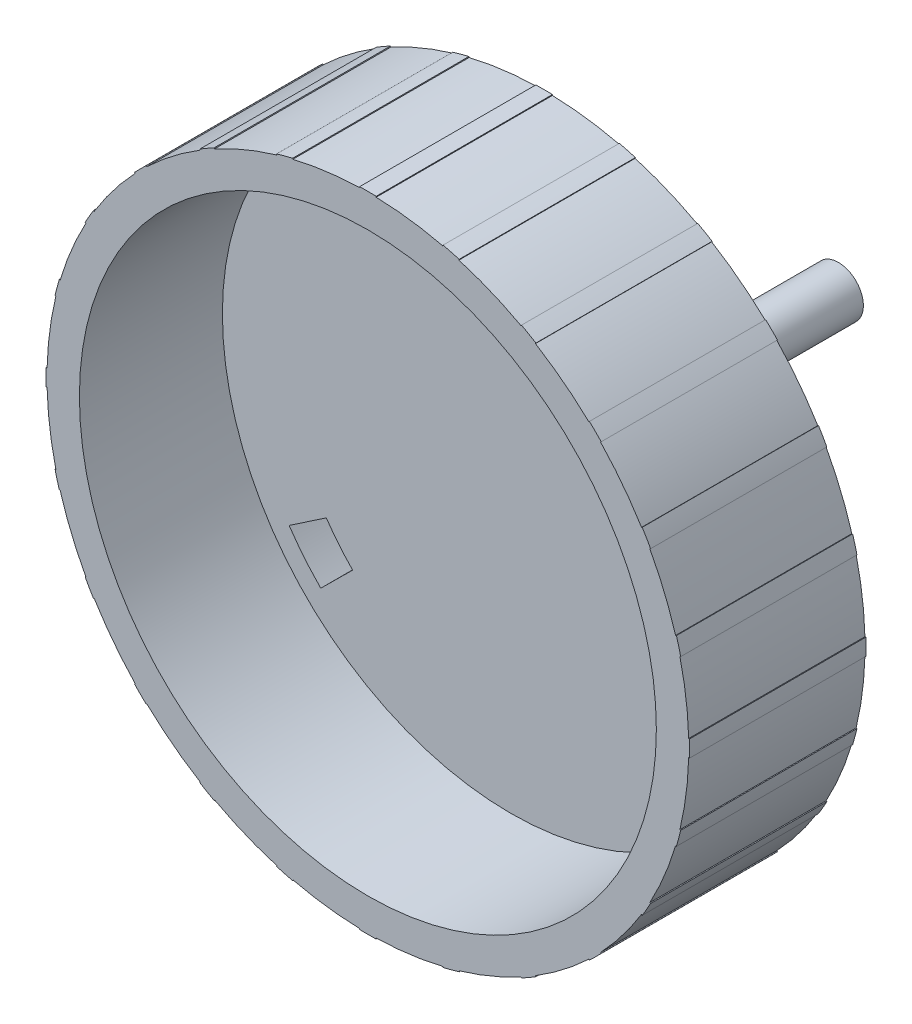
SolidWorks part; units mm, degrees
ref_plane "Front Plane" through (0, 0, 0) normal (0, 0, 1) x (1, 0, 0)
ref_plane "Top Plane" through (0, 0, 0) normal (0, 1, 0) x (1, 0, 0)
ref_plane "Right Plane" through (0, 0, 0) normal (1, 0, 0) x (0, 0, -1)
sketch "Sketch1" plane through (0, 0, 0) normal (0, 0, 1) x (1, 0, 0)
  line L0 (0, 19.3) -> (0, -19.3) construction
  line L1 (-19.3, 0) -> (19.3, 0) construction
  circle A0 centre (0, 0) radius 19.3
  dimension "D1" = 38.6
extrude "Boss-Extrude1" add sketch "Sketch1" along normal blind 10.6
sketch "Sketch3" plane through (0, 0, 10.6) normal (0, 0, 1) x (1, 0, 0)
  line L0 (0, 0) -> (0.5, 19.3435) construction
  line L1 (0, 0) -> (-0.5, 19.3435) construction
  line L2 (0, 0) -> (0, 19.35)
  line L3 (-0.5, 19.3435) -> (0.5, 19.3435) construction
  line L4 (-0.5, 19.3435) -> (-0.4987, 19.2936)
  line L5 (0.5, 19.3435) -> (0.4987, 19.2936)
  arc A0 (0.5, 19.3435) -> (-0.5, 19.3435) centre (0, 0) ccw
  circle A1 centre (0, 0) radius 19.3 construction
  arc A2 (0.4987, 19.2936) -> (-0.4987, 19.2936) centre (0, 0) ccw
  point P3 (0, 19.3435)
  dimension "D1" = 0.05
  dimension "D2" = 1
extrude "Boss-Extrude3" add sketch "Sketch3" against normal through all contours A0 L4 A2 L5
sketch "Sketch8" plane through (0, 0, 10.6) normal (0, 0, 1) x (1, 0, 0)
  circle A0 centre (0, 0) radius 17.35
  arc A2 (0.5, 19.3435) -> (-0.5, 19.3435) centre (0, 0) ccw construction
  dimension "D1" = 2
extrude "Cut-Extrude2" cut sketch "Sketch8" against normal offset from surface (8.6 mm away) 2 up to face at (0, 9.6718, 0)
pattern_circular "CirPattern1" count 24 over 360 about axis through (0, 0, 10.6) along (0, 0, 1) of "Boss-Extrude3"
sketch "Sketch5" plane through (0, 0, 0) normal (0, 1, 0) x (1, 0, 0)
  line L0 (0, 0) -> (4, 0)
  line L1 (4.5118, 0) -> (0.4987, 0) construction
  line L2 (4, 0) -> (2.95, 1.05)
  line L3 (2.95, 1.05) -> (2.95, 8)
  line L4 (2.95, 8) -> (0, 8)
  line L5 (0, 8) -> (0, 0)
  dimension "D1" = 2.95
  dimension "D2" = 4
  dimension "D3" = 45
  dimension "D4" = 8
revolve "Revolve1" add sketch "Sketch5" angle 360 about L5
sketch "Sketch6" plane through (0, 0, -8) normal (0, 0, -1) x (-1, 0, 0)
  line L0 (0.95, 1.1608) -> (0.95, -1.1608)
  line L1 (0.95, 0) -> (-1.5, 0) construction
  arc A0 (0.95, 1.1608) -> (0.95, -1.1608) centre (0, 0) ccw
  circle A1 centre (0, 0) radius 1.5 construction
  dimension "D1" = 3
  dimension "D2" = 2.45
extrude "Boss-Extrude4" add sketch "Sketch6" along normal blind 9.7
sketch "Sketch7" plane through (0, 0, 0) normal (0, 0, -1) x (-1, 0, 0)
  line L0 (0, 0) -> (1.1414, 16.0595) construction
  line L1 (0, 0) -> (4.101, 15.5689) construction
  line L2 (1.1414, 16.0595) -> (0.95, 13.3663)
  line L3 (0.95, 13.3663) -> (0.95, 1.1608) construction
  line L4 (4.101, 15.5689) -> (3.4133, 12.958)
  arc A0 (4.101, 15.5689) -> (1.1414, 16.0595) centre (0, 0) ccw
  arc A1 (3.4133, 12.958) -> (0.95, 13.3663) centre (0, 0) ccw
  arc A3 (9.2149, 16.9581) -> (5.4753, 18.5071) centre (0, 0) ccw construction
  dimension "D1" = 2.7
  dimension "D2" = 3.2
  dimension "D3" = 3
extrude "Cut-Extrude1" cut sketch "Sketch7" against normal through all
sketch "Sketch9" plane through (0, 0, 0) normal (0, 0, -1) x (-1, 0, 0)
  line L0 (3.4133, 12.958) -> (4.101, 15.5689) construction
  line L1 (3.4133, 12.958) -> (4.101, 15.5689)
  line L2 (4.101, 15.5689) -> (5.0597, 15.2843)
  line L3 (5.0597, 15.2843) -> (0, 0) construction
  line L4 (5.0597, 15.2843) -> (4.2112, 12.7211) construction
  arc A0 (3.4133, 12.958) -> (0.95, 13.3663) centre (0, 0) ccw construction
  arc A1 (4.101, 15.5689) -> (1.1414, 16.0595) centre (0, 0) ccw construction
  arc A2 (3.4133, 12.958) -> (0.95, 13.3663) centre (0, 0) ccw construction
  arc A3 (4.101, 15.5689) -> (1.1414, 16.0595) centre (0, 0) ccw construction
  arc A4 (5.0597, 15.2843) -> (1.1414, 16.0595) centre (0, 0) ccw
  arc A5 (4.2112, 12.7211) -> (0.95, 13.3663) centre (0, 0) ccw
  arc A6 (5.0597, 15.2843) -> (4.2112, 12.7211) centre (4.6354, 14.0027) cw
  dimension "D1" = 1
extrude "Boss-Extrude5" add sketch "Sketch9" along normal blind 0.1 contours A6 L2 L1 A5 region at (-4.7298, 13.9856, 0)
pattern_circular "CirPattern2" count 3 over 360 about axis through (0, 0, -1.05) along (0, 0, -1) of "Cut-Extrude1", "Boss-Extrude5"
